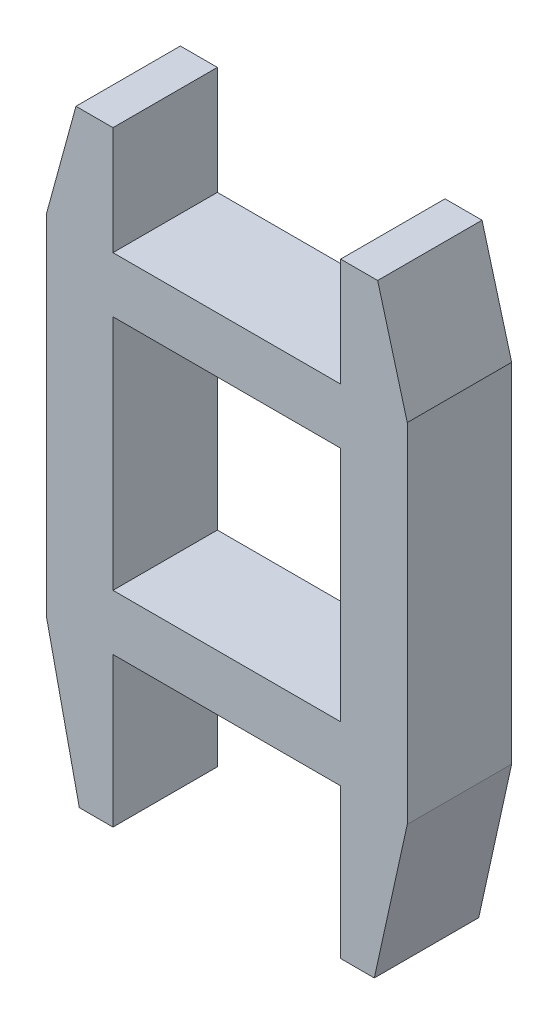
SolidWorks part; units mm, degrees
material "Acrylic (Medium-high impact)"
ref_plane "Front Plane" through (0, 0, 0) normal (0, 0, 1) x (1, 0, 0)
ref_plane "Top Plane" through (0, 0, 0) normal (0, 1, 0) x (1, 0, 0)
ref_plane "Right Plane" through (0, 0, 0) normal (1, 0, 0) x (0, 0, -1)
sketch "Sketch1" plane through (0, 0, 0) normal (0, 0, 1) x (1, 0, 0)
  line L0 (1247.2596, 962.2772) -> (1247.2596, 949.4772)
  line L1 (1263.1596, 947.9772) -> (1243.6596, 947.9772) construction
  line L2 (1247.2596, 946.4772) -> (1243.6596, 946.4772) construction
  line L3 (1247.2596, 962.2772) -> (1259.5596, 962.2772)
  line L4 (1245.2596, 971.1264) -> (1247.2596, 971.1264)
  line L5 (1247.2596, 971.1264) -> (1247.2596, 965.2772)
  line L6 (1247.2596, 955.8772) -> (1259.5596, 955.8772) construction
  line L7 (1259.5596, 965.2772) -> (1247.2596, 965.2772)
  line L8 (1243.6596, 965.2772) -> (1243.6596, 946.4772)
  line L9 (1243.6596, 946.4772) -> (1245.4404, 938.398)
  line L10 (1247.2596, 965.2772) -> (1243.6596, 965.2772) construction
  line L11 (1259.5596, 946.4772) -> (1247.2596, 946.4772)
  line L12 (1243.6596, 965.2772) -> (1245.2596, 971.1264)
  line L13 (1247.2596, 938.398) -> (1247.2596, 946.4772)
  line L14 (1245.4404, 938.398) -> (1247.2596, 938.398)
  line L15 (1247.2596, 949.4772) -> (1259.5596, 949.4772)
  line L16 (1259.5596, 965.2772) -> (1263.1596, 965.2772) construction
  line L17 (1259.5596, 946.4772) -> (1263.1596, 946.4772) construction
  line L18 (1261.3789, 938.398) -> (1259.5596, 938.398)
  line L19 (1253.4096, -39.6851) -> (1253.4096, 49960.3149) construction
  line L20 (1259.5596, 938.398) -> (1259.5596, 946.4772)
  line L21 (1263.1596, 965.2772) -> (1261.5596, 971.1264)
  line L22 (1263.1596, 946.4772) -> (1261.3789, 938.398)
  line L23 (1263.1596, 965.2772) -> (1263.1596, 946.4772)
  line L24 (1259.5596, 971.1264) -> (1259.5596, 965.2772)
  line L25 (1261.5596, 971.1264) -> (1259.5596, 971.1264)
  line L26 (1263.1596, 963.7772) -> (1243.6596, 963.7772) construction
  line L27 (1259.5596, 962.2772) -> (1259.5596, 949.4772)
  point P2 (1263.1596, 955.8772)
  point P14 (1243.6596, 955.8772)
  point P15 (1253.4096, 965.2772)
  point P20 (1253.4096, 963.7772)
  point P26 (1253.4096, 955.8772)
  point P28 (1253.4096, 965.2772)
  point P30 (1253.4096, 962.2772)
  point P31 (1253.4096, 947.9772)
  point P33 (1253.4096, 949.4772)
  point P36 (1253.4096, 946.4772)
  point P38 (1253.4096, 962.2772)
  dimension "D1" = 6.15
  dimension "D2" = 5.8492
  dimension "D3" = 2
  dimension "D4" = 3
  dimension "D5" = 9.4
  dimension "D6" = 8.0792
  dimension "D7" = 192.43
  dimension "D8" = 3.6
extrude "Boss-Extrude1" add sketch "Sketch1" along normal blind 5.64
